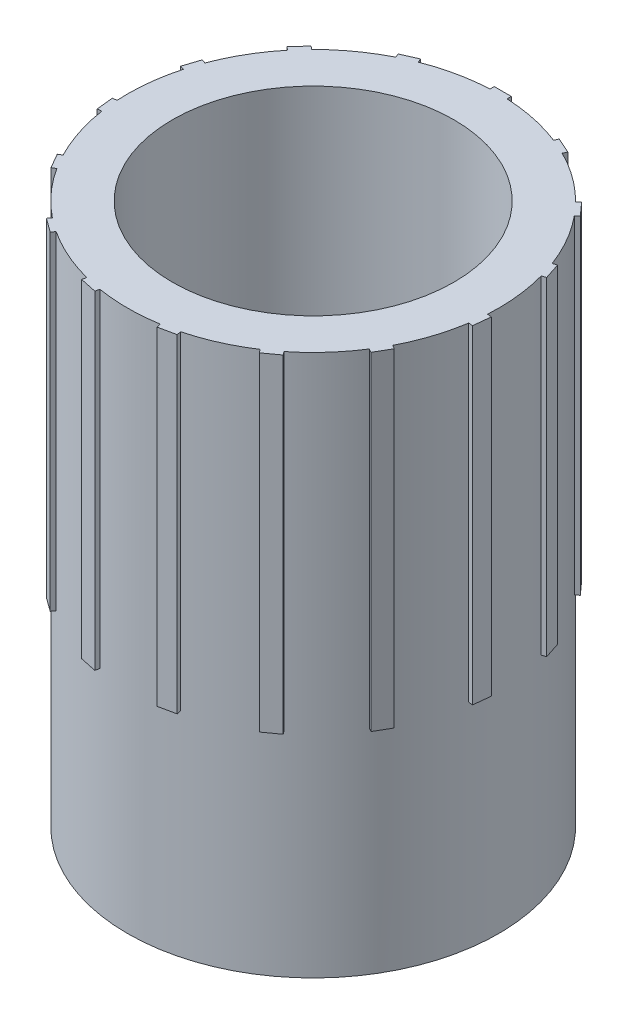
SolidWorks part; units mm, degrees
ref_plane "Front Plane" through (0, 0, 0) normal (0, 0, 1) x (1, 0, 0)
ref_plane "Top Plane" through (0, 0, 0) normal (0, 1, 0) x (1, 0, 0)
ref_plane "Right Plane" through (0, 0, 0) normal (1, 0, 0) x (0, 0, -1)
sketch "Sketch1" plane through (0, 0, 0) normal (0, 1, 0) x (1, 0, 0)
  circle A0 centre (0, 0) radius 4.35
  dimension "D1" = 8.7
extrude "Body" add sketch "Sketch1" along normal blind 12.7
sketch "Sketch2" plane through (0, 12.7, 0) normal (0, 1, 0) x (1, 0, 0)
  line L2 (-0.2, 4.3454) -> (-0.2, 4.4454)
  line L3 (-0.2, 4.4454) -> (0.2, 4.4454)
  line L4 (0.2, 4.3454) -> (0.2, 4.4454)
  circle A0 centre (0, 0) radius 4.35 construction
  arc A1 (0.2, 4.3454) -> (-0.2, 4.3454) centre (0, 0) ccw
  dimension "D1" = 0.1
  dimension "D2" = 0.2
  dimension "D3" = 0.4
extrude "Teeth" add sketch "Sketch2" against normal offset from surface (7.7 mm away) 5 up to face at (0, 0, 4.35)
pattern_circular "CirPattern1" count 15 over 360 about axis through (0, 12.7, 0) along (0, -1, 0) of "Teeth" reverse direction yes
hole_wizard "M6 Clearance Hole1" positions "Sketch3" profile "Sketch4" hole size "M6" standard "ANSI Metric" end condition through all
sketch "Sketch3" plane through (0, 12.7, 0) normal (0, 1, 0) x (1, 0, 0)
  point P0 (0, 0)
sketch "Sketch4" plane through (0, 12.7, 0) normal (1, 0, 0) x (0, 0, 1)
  line L0 (0, 0) -> (0, 12.7)
  line L1 (0, 12.7) -> (3.3, 12.7)
  line L2 (3.3, 12.7) -> (3.3, 0)
  line L5 (3.3, 0) -> (0, 0)
  line L11 (0, -6.35) -> (0, 107.95) construction
  dimension "Thru Hole Dia." = 6.6
  dimension "Thru Hole Depth" = 12.7
